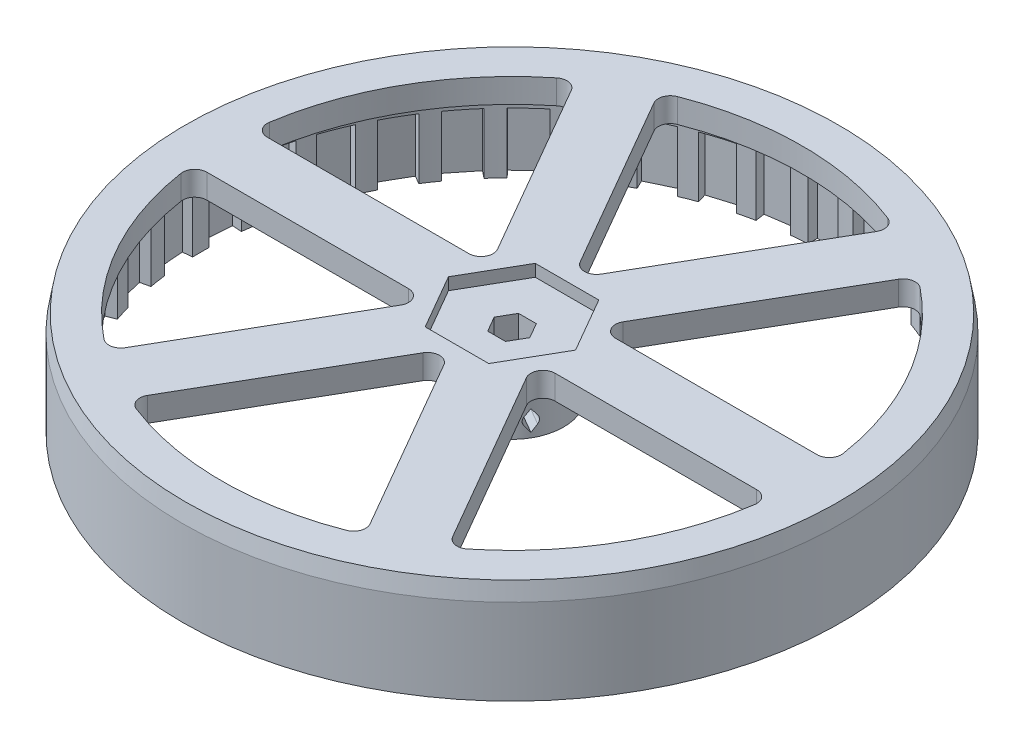
SolidWorks part; units mm, degrees
material "ABS"
ref_plane "Front Plane" through (0, 0, 0) normal (0, 0, 1) x (1, 0, 0)
ref_plane "Top Plane" through (0, 0, 0) normal (0, 1, 0) x (1, 0, 0)
ref_plane "Right Plane" through (0, 0, 0) normal (1, 0, 0) x (0, 0, -1)
sketch "Sketch1" plane through (0, 0, 0) normal (0, 0, 1) x (1, 0, 0)
  line L0 (0, 29) -> (0, 33)
  line L4 (51.5, 29) -> (51.5, 16)
  line L5 (51.5, 16) -> (54.5, 16)
  line L6 (54.5, 16) -> (54.5, 33)
  line L7 (54.5, 33) -> (0, 33)
  line L8 (0, 0) -> (0, 63.0003) construction
  line L11 (0, 29) -> (51.5, 29)
  dimension "D3" = 103
  dimension "D4" = 3
  dimension "D7" = 13
  dimension "D8" = 4
revolve "Main Revolve" add sketch "Sketch1" angle 360 about L8
sketch "Sketch2" plane through (0, 33, 0) normal (0, 1, 0) x (1, 0, 0)
  line L0 (0, 0) -> (0, 75.8468) construction
  line L1 (0, 0) -> (27.25, 47.1984) construction
  line L2 (18.402, 41.8732) -> (1.7321, 13)
  line L3 (-18.402, 41.8732) -> (-1.7321, 13)
  line L4 (0, 0) -> (-27.25, 47.1984) construction
  arc A0 (-17.3947, 44.7373) -> (17.3947, 44.7373) centre (0, 0) cw
  circle A2 centre (0, 0) radius 54.5 construction
  arc A3 (17.3947, 44.7373) -> (18.402, 41.8732) centre (16.67, 42.8732) cw
  arc A6 (-17.3947, 44.7373) -> (-18.402, 41.8732) centre (-16.67, 42.8732) ccw
  arc A8 (1.7321, 13) -> (-1.7321, 13) centre (0, 14) cw
  point P15 (0, 10)
  point P23 (0, 10)
  dimension "D5" = 48
  dimension "D6" = 2
  dimension "D7" = 2
  dimension "D3" = 2
  dimension "D1" = 30
  dimension "D2" = 30
  dimension "D4" = 10
extrude "Slot Cut" cut sketch "Sketch2" against normal through all
pattern_circular "Slot Cut Pattern" count 6 over 360 about axis through (0, 33, 0) along (0, -1, 0) of "Slot Cut"
sketch "Sketch4" plane through (0, 16, 0) normal (0, -1, 0) x (1, 0, 0)
  line L0 (-2.5, 53) -> (2.5, 53)
  line L1 (-2.5, 53) -> (-2.5, 51.4393)
  line L2 (2.5, 53) -> (2.5, 51.4393)
  circle A0 centre (0, 0) radius 51.5 construction
  arc A1 (2.5, 51.4393) -> (-2.5, 51.4393) centre (0, 0) ccw
  point P3 (0, 53)
  dimension "D2" = 1.5
  dimension "D1" = 5
extrude "Magnet Slots" cut sketch "Sketch4" against normal blind 10
pattern_circular "Magnet Cut Pattern" count 42 over 360 about axis through (0, 16, 0) along (0, -1, 0) of "Magnet Slots"
chamfer "Chamfer1" distance 0.5 angle 80 1 edges at (0, 33, -54.5) first distance on face at (0, 33, 33.6578)
sketch "Sketch5" plane through (0, 33, 0) normal (0, 1, 0) x (1, 0, 0)
  line L1 (2.9445, 0) -> (1.4722, 2.55)
  line L2 (1.4722, 2.55) -> (-1.4722, 2.55)
  line L3 (-1.4722, 2.55) -> (-2.9445, 0)
  line L4 (-2.9445, 0) -> (-1.4722, -2.55)
  line L5 (-1.4722, -2.55) -> (1.4722, -2.55)
  line L6 (1.4722, -2.55) -> (2.9445, 0)
  circle A0 centre (0, 0) radius 2.55 construction
  dimension "D1" = 5.1
extrude "Cut-Extrude1" cut sketch "Sketch5" against normal through all both and the other way through all
sketch "Sketch8" plane through (0, 29, 0) normal (0, -1, 0) x (1, 0, 0)
  line L0 (-1.4722, 2.55) -> (1.4722, 2.55) construction
  line L1 (2.9445, 0) -> (1.4722, 2.55)
  line L2 (1.4722, 2.55) -> (-1.4722, 2.55)
  line L3 (-1.4722, 2.55) -> (-2.9445, 0)
  line L4 (-2.9445, 0) -> (-1.4722, -2.55)
  line L5 (-1.4722, -2.55) -> (1.4722, -2.55)
  line L6 (1.4722, -2.55) -> (2.9445, 0)
  circle A0 centre (0, 0) radius 2.55 construction
  circle A1 centre (0, 0) radius 8.55
  dimension "D1" = 17.1
extrude "Boss-Extrude1" add sketch "Sketch8" along normal blind 8
sketch "Sketch9" plane through (0, 29, 0) normal (0, -1, 0) x (1, 0, 0)
  circle A0 centre (0, 0) radius 8.55
  circle A1 centre (0, 0) radius 9.05
  circle A2 centre (0, 0) radius 8.55 construction
  dimension "D1" = 0.5
extrude "Boss-Extrude2" add sketch "Sketch9" along normal blind 1
sketch "Sketch10" plane through (-2.2084, 0, -1.275) normal (0.866, 0, 0.5) x (0.5, 0, -0.866)
  line L0 (0, 26) -> (0, 21) construction
  line L2 (-1.4722, 21) -> (1.4722, 21) construction
  line L4 (2, 26) -> (-2, 26)
  line L5 (2, 26) -> (2, 21)
  line L6 (2, 21) -> (-2, 21)
  line L7 (-2, 26) -> (-2, 21)
  line L8 (2, 26) -> (-2, 21) construction
  line L9 (2, 21) -> (-2, 26) construction
  point P6 (0, 23.5)
  dimension "D1" = 4
  dimension "D2" = 5
extrude "Cut-Extrude2" cut sketch "Sketch10" against normal blind 1.6 and the other way blind 1.6
extrude "Cut-Extrude3" cut sketch "Sketch10<2>" along normal blind 1.6 and the other way blind 1.6 from surface starting at face at (2.2084, 27, 1.275)
sketch "Sketch10<2>" plane through (-2.2084, 0, -1.275) normal (0.866, 0, 0.5) x (0.5, 0, -0.866) same geometry as "Sketch10"
fillet "Fillet1" radius 0.5 4 edges at (-0.4167, 23.5, -2.55) (2.4167, 23.5, -0.9141) (0.4167, 23.5, 2.55) (-2.4167, 23.5, 0.9141)
sketch "Sketch11" plane through (-3.594, 0, -2.075) normal (0.866, 0, 0.5) x (0.5, 0, -0.866)
  line L0 (0, 26) -> (0, 21) construction
  line L1 (2, 26) -> (-2, 26) construction
  line L2 (-2, 21) -> (2, 21) construction
  line L3 (0, 23.5) -> (0, 21.8) construction
  line L4 (0, 21.8) -> (-0.8258, 22.8515)
  line L5 (0, 21.8) -> (0.8258, 22.8515)
  line L6 (0, 23.5) -> (0.5997, 23.5) construction
  line L7 (0, 25.2) -> (-0.8258, 24.1485)
  line L8 (0, 25.2) -> (0.8258, 24.1485)
  arc A0 (-0.8258, 24.1485) -> (-0.8258, 22.8515) centre (0, 23.5) ccw
  arc A1 (0.8258, 22.8515) -> (0.8258, 24.1485) centre (0, 23.5) ccw
  dimension "D1" = 2.1
  dimension "D2" = 1.7
extrude "Cut-Extrude4" cut sketch "Sketch11" against normal up to next and the other way blind 15.5 contours L7 A0 L4 L5 A1 L8
sketch "Sketch14" plane through (0, 33, 0) normal (0, 1, 0) x (1, 0, 0)
  line L0 (2.9445, 0) -> (1.4722, 2.55) construction
  line L1 (5.2539, -9.1) -> (10.5078, 0)
  line L2 (10.5078, 0) -> (5.2539, 9.1)
  line L3 (5.2539, 9.1) -> (-5.2539, 9.1)
  line L4 (-5.2539, 9.1) -> (-10.5078, 0)
  line L5 (-10.5078, 0) -> (-5.2539, -9.1)
  line L6 (-5.2539, -9.1) -> (5.2539, -9.1)
  circle A3 centre (0, 0) radius 9.1 construction
  dimension "D1" = 18.2
extrude "Cut-Extrude6" cut sketch "Sketch14" against normal blind 2
equation "\"D3@Sketch1\"=100+2*(1+0.5)"
